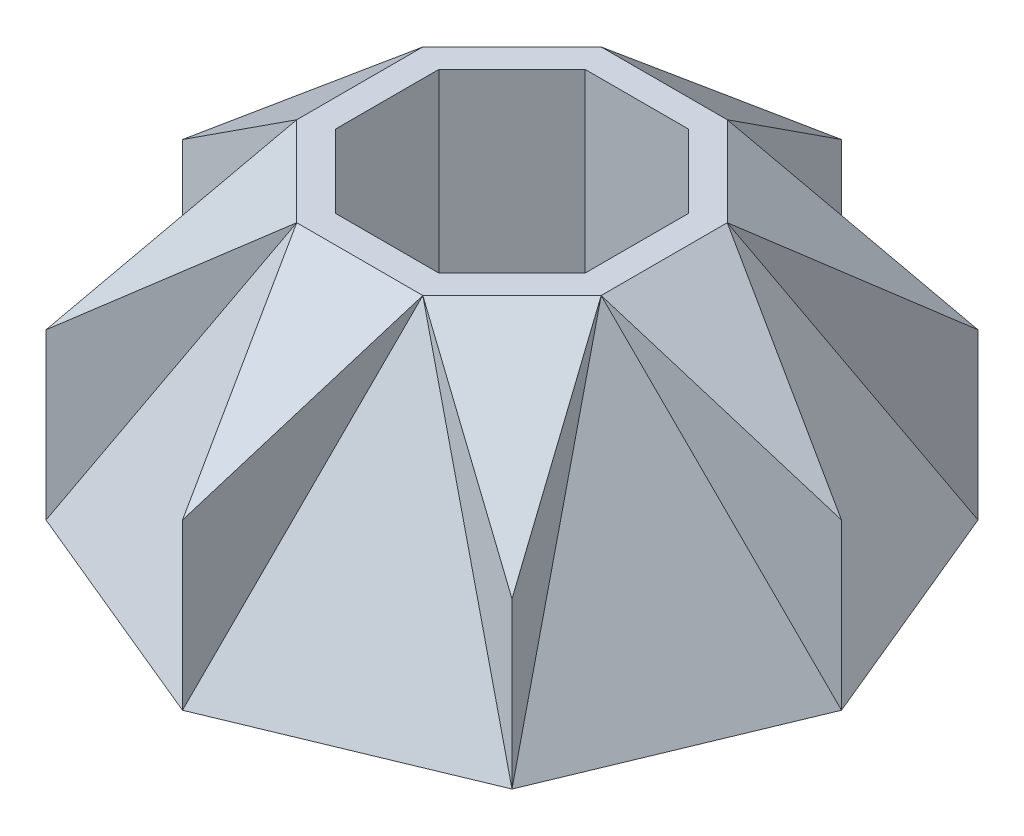
SolidWorks part; units mm, degrees
ref_plane "前视基准面" through (0, 0, 0) normal (0, 0, 1) x (1, 0, 0)
ref_plane "上视基准面" through (0, 0, 0) normal (0, 1, 0) x (1, 0, 0)
ref_plane "右视基准面" through (0, 0, 0) normal (1, 0, 0) x (0, 0, -1)
other "Configuration Table"
sketch "草图1" plane through (0, 0, 0) normal (0, 1, 0) x (1, 0, 0)
  line L1 (0, 60) -> (-42.4264, 42.4264)
  line L2 (-42.4264, 42.4264) -> (-60, 0)
  line L3 (-60, 0) -> (-42.4264, -42.4264)
  line L4 (-42.4264, -42.4264) -> (0, -60)
  line L5 (0, -60) -> (42.4264, -42.4264)
  line L6 (42.4264, -42.4264) -> (60, 0)
  line L7 (60, 0) -> (42.4264, 42.4264)
  line L8 (42.4264, 42.4264) -> (0, 60)
  circle A0 centre (0, 0) radius 55.4328 construction
  dimension "D1" = 120
ref_plane "基准面1" through (0, 55, 0) normal (0, 1, 0) x (1, 0, 0)
sketch "草图2" plane through (0, 55, 0) normal (0, 1, 0) x (1, 0, 0)
  line L1 (11.4805, 27.7164) -> (-11.4805, 27.7164)
  line L2 (-11.4805, 27.7164) -> (-27.7164, 11.4805)
  line L3 (-27.7164, 11.4805) -> (-27.7164, -11.4805)
  line L4 (-27.7164, -11.4805) -> (-11.4805, -27.7164)
  line L5 (-11.4805, -27.7164) -> (11.4805, -27.7164)
  line L6 (11.4805, -27.7164) -> (27.7164, -11.4805)
  line L7 (27.7164, -11.4805) -> (27.7164, 11.4805)
  line L8 (27.7164, 11.4805) -> (11.4805, 27.7164)
  circle A0 centre (0, 0) radius 27.7164 construction
  dimension "D1" = 60
sketch "草图7" plane through (0, 55, 0) normal (0, 1, 0) x (1, 0, 0)
  line L1 (0, 32.4718) -> (-22.961, 22.961)
  line L2 (-22.961, 22.961) -> (-32.4718, 0)
  line L3 (-32.4718, 0) -> (-22.961, -22.961)
  line L4 (-22.961, -22.961) -> (0, -32.4718)
  line L5 (0, -32.4718) -> (22.961, -22.961)
  line L6 (22.961, -22.961) -> (32.4718, 0)
  line L7 (32.4718, 0) -> (22.961, 22.961)
  line L8 (22.961, 22.961) -> (0, 32.4718)
  circle A0 centre (0, 0) radius 30 construction
loft "放样4" add profiles "草图7", "草图1"
sketch "草图9" plane through (0, 55, 0) normal (0, 1, 0) x (1, 0, 0)
  line L0 (27.7164, 11.4805) -> (60, 0)
  line L1 (60, 0) -> (27.7164, -11.4805)
  line L2 (27.7164, -11.4805) -> (27.7164, 11.4805)
extrude "凸台-拉伸1" add sketch "草图9" against normal up to body
sketch "草图10" plane through (0, 0, 0) normal (0, 0, 1) x (1, 0, 0)
  line L0 (27.7164, 55) -> (60, 30)
  line L1 (27.7164, 55) -> (11.4805, 55) construction
  line L2 (27.7164, 55) -> (-27.7164, 55) construction
  line L3 (60, 0) -> (60, 55) construction
  point P8 (0, 0)
  dimension "D1" = 30
extrude "切除-拉伸2" cut sketch "草图10" against normal through all and the other way through all
ref_axis "基准轴1" through (0, 58.1018, 0) along (0, -1, 0)
pattern_circular "阵列(圆周)2" count 8 over 360 about axis through (0, 58.1018, 0) along (0, -1, 0) of "凸台-拉伸1", "切除-拉伸2"
sketch "草图12" plane through (0, 55, 0) normal (0, 1, 0) x (1, 0, 0)
  line L16 (22.7164, -9.4094) -> (22.7164, 9.4094)
  line L17 (22.7164, 9.4094) -> (9.4094, 22.7164)
  line L18 (9.4094, 22.7164) -> (-9.4094, 22.7164)
  line L19 (-9.4094, 22.7164) -> (-22.7164, 9.4094)
  line L20 (-22.7164, 9.4094) -> (-22.7164, -9.4094)
  line L21 (-22.7164, -9.4094) -> (-9.4094, -22.7164)
  line L22 (-9.4094, -22.7164) -> (9.4094, -22.7164)
  line L23 (9.4094, -22.7164) -> (22.7164, -9.4094)
  line L24 (22.7164, -9.4094) -> (22.7164, 9.4094)
  line L25 (22.7164, 9.4094) -> (9.4094, 22.7164)
  line L26 (9.4094, 22.7164) -> (-9.4094, 22.7164)
  line L27 (-9.4094, 22.7164) -> (-22.7164, 9.4094)
  line L28 (-22.7164, 9.4094) -> (-22.7164, -9.4094)
  line L29 (-22.7164, -9.4094) -> (-9.4094, -22.7164)
  line L30 (-9.4094, -22.7164) -> (9.4094, -22.7164)
  line L31 (9.4094, -22.7164) -> (22.7164, -9.4094)
  dimension "D1" = 5
extrude "切除-拉伸3" cut sketch "草图12" against normal through all
